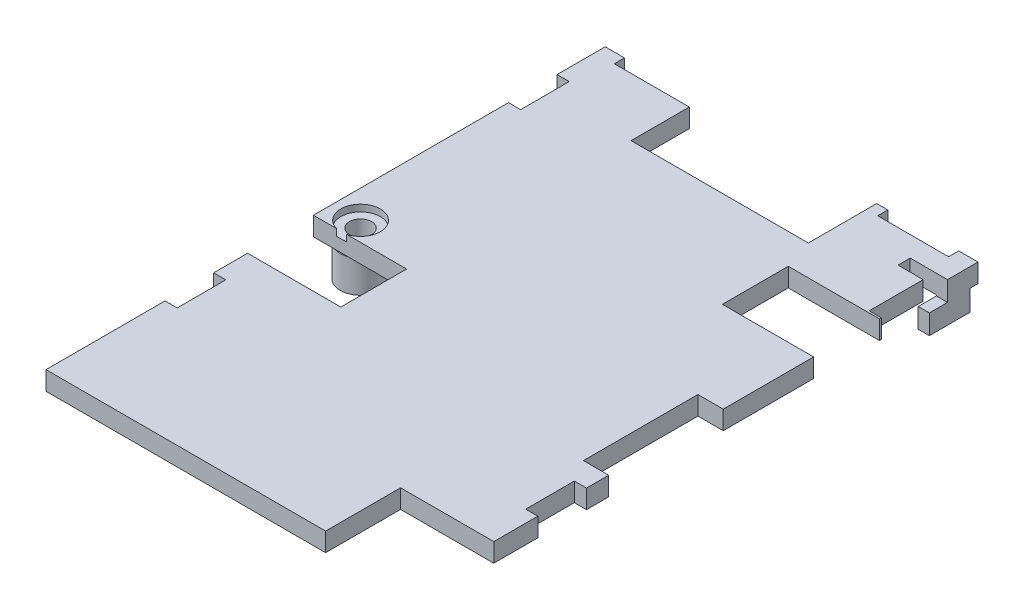
SolidWorks part; units mm, degrees
ref_plane "Front Plane" through (0, 0, 0) normal (0, 0, 1) x (1, 0, 0)
ref_plane "Top Plane" through (0, 0, 0) normal (0, 1, 0) x (1, 0, 0)
ref_plane "Right Plane" through (0, 0, 0) normal (1, 0, 0) x (0, 0, -1)
other "Configuration Table"
sketch "Sketch1" plane through (0, 0, 0) normal (0, 1, 0) x (1, 0, 0)
  line L1 (-18.4, 33.55) -> (18.4, 33.55)
  line L2 (-18.4, 33.55) -> (-18.4, -21.65)
  line L3 (-18.4, -21.65) -> (18.4, -21.65)
  line L4 (18.4, 33.55) -> (18.4, -21.65)
extrude "Tray" add sketch "Sketch1" along normal blind 1.85 from offset 4.75
sketch "Sketch2" plane through (0, 0, 0) normal (0, 1, 0) x (1, 0, 0)
  line L1 (-18.45, 4.75) -> (-9.2, 4.75)
  line L2 (-18.45, 4.75) -> (-18.45, -1.75)
  line L3 (-18.45, -1.75) -> (-9.2, -1.75)
  line L4 (-9.2, 4.75) -> (-9.2, -1.75)
  line L6 (9.4, 23.82) -> (18.45, 23.82)
  line L7 (9.4, 23.82) -> (9.4, 17.32)
  line L8 (9.4, 17.32) -> (18.45, 17.32)
  line L9 (18.45, 23.82) -> (18.45, 17.32)
  line L11 (9.2, -14.25) -> (18.45, -14.25)
  line L12 (9.2, -14.25) -> (9.2, -21.75)
  line L13 (9.2, -21.75) -> (18.45, -21.75)
  line L14 (18.45, -14.25) -> (18.45, -21.75)
extrude "S1-S3 and plugs" cut sketch "Sketch2" along normal blind 2.05 from offset 4.65
sketch "Sketch3" plane through (0, 0, 0) normal (0, 1, 0) x (1, 0, 0)
  line L1 (-9.1, 33.65) -> (8.4, 33.65)
  line L2 (-9.1, 33.65) -> (-9.1, 26.8)
  line L3 (-9.1, 26.8) -> (8.4, 26.8)
  line L4 (8.4, 33.65) -> (8.4, 26.8)
extrude "J4 and its flex" cut sketch "Sketch3" along normal blind 2.05 from offset 4.65
sketch "Sketch4" plane through (0, 0, 0) normal (0, 1, 0) x (1, 0, 0)
  line L1 (15.9, 8.4) -> (18.5, 8.4)
  line L2 (15.9, 8.4) -> (15.9, -2.9)
  line L3 (15.9, -2.9) -> (18.5, -2.9)
  line L4 (18.5, 8.4) -> (18.5, -2.9)
extrude "Battery and NTC pad slot" cut sketch "Sketch4" along normal blind 2.05 from offset 4.65
sketch "Sketch5" plane through (0, 0, 0) normal (0, 1, 0) x (1, 0, 0)
  line L1 (17.3, 32.75) -> (18.4, 32.75)
  line L2 (17.3, 32.75) -> (17.3, 28.75)
  line L3 (17.3, 28.75) -> (18.4, 28.75)
  line L4 (18.4, 32.75) -> (18.4, 28.75)
  line L6 (-18.4, 32.75) -> (-17.3, 32.75)
  line L7 (-18.4, 32.75) -> (-18.4, 28.75)
  line L8 (-18.4, 28.75) -> (-17.3, 28.75)
  line L9 (-17.3, 32.75) -> (-17.3, 28.75)
extrude "Alignment rails" add sketch "Sketch5" along normal blind 2.06 from offset 2.7
sketch "Sketch6" plane through (0, 0, 0) normal (0, 1, 0) x (1, 0, 0)
  circle A0 centre (-15.64, 6.64) radius 2
extrude "Board screw foot" add sketch "Sketch6" along normal blind 3.16 from offset 1.6
sketch "Sketch7" plane through (0, 0, 0) normal (0, 1, 0) x (1, 0, 0)
  circle A0 centre (-15.64, 6.64) radius 1.1
extrude "Board screw hole" cut sketch "Sketch7" along normal blind 5.2 from offset 1.5
sketch "Sketch8" plane through (0, 0, 0) normal (0, 1, 0) x (1, 0, 0)
  circle A0 centre (-15.64, 6.64) radius 1.95
extrude "Board screw counterbore" cut sketch "Sketch8" along normal blind 0.76 from offset 5.94
sketch "Sketch9" plane through (0, 0, 0) normal (0, 1, 0) x (1, 0, 0)
  line L1 (14.72, 30.54) -> (18.5, 30.54)
  line L2 (14.72, 30.54) -> (14.72, 29.34)
  line L3 (14.72, 29.34) -> (18.5, 29.34)
  line L4 (18.5, 30.54) -> (18.5, 29.34)
extrude "Mic slot" cut sketch "Sketch9" along normal blind 2.05 from offset 4.65
sketch "Sketch10" plane through (0, 0, 0) normal (0, 1, 0) x (1, 0, 0)
  line L1 (17.2, 30.54) -> (18.5, 30.54)
  line L2 (17.2, 30.54) -> (17.2, 24)
  line L3 (17.2, 24) -> (18.5, 24)
  line L4 (18.5, 30.54) -> (18.5, 24)
  line L6 (-18.5, 28.8) -> (-17.2, 28.8)
  line L7 (-18.5, 28.8) -> (-18.5, 24)
  line L8 (-18.5, 24) -> (-17.2, 24)
  line L9 (-17.2, 28.8) -> (-17.2, 24)
  line L11 (17.2, -5.1) -> (18.5, -5.1)
  line L12 (17.2, -5.1) -> (17.2, -9.9)
  line L13 (17.2, -9.9) -> (18.5, -9.9)
  line L14 (18.5, -5.1) -> (18.5, -9.9)
  line L16 (-18.5, -5.1) -> (-17.2, -5.1)
  line L17 (-18.5, -5.1) -> (-18.5, -9.9)
  line L18 (-18.5, -9.9) -> (-17.2, -9.9)
  line L19 (-17.2, -5.1) -> (-17.2, -9.9)
  line L21 (9.5, 33.65) -> (16.5, 33.65)
  line L22 (9.5, 33.65) -> (9.5, 32.55)
  line L23 (9.5, 32.55) -> (16.5, 32.55)
  line L24 (16.5, 33.65) -> (16.5, 32.55)
  line L26 (-16.5, 33.65) -> (-9, 33.65)
  line L27 (-16.5, 33.65) -> (-16.5, 32.55)
  line L28 (-16.5, 32.55) -> (-9, 32.55)
  line L29 (-9, 33.65) -> (-9, 32.55)
extrude "Snap clip room" cut sketch "Sketch10" along normal blind 2.05 from offset 4.65
